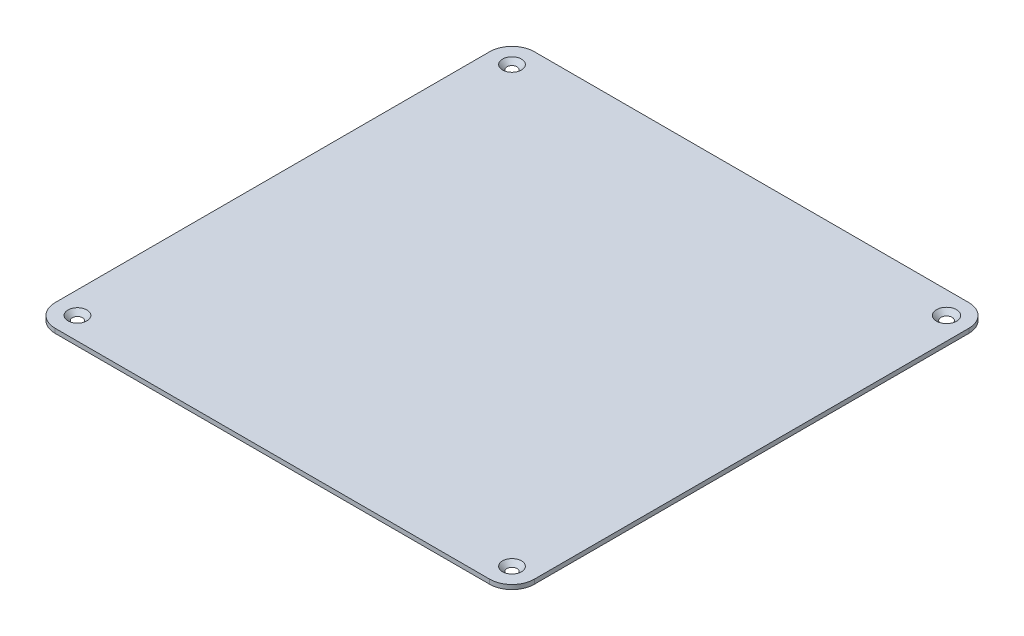
SolidWorks part; units mm, degrees
ref_plane "Front" through (0, 0, 0) normal (0, 0, 1) x (1, 0, 0)
ref_plane "Top" through (0, 0, 0) normal (0, 1, 0) x (1, 0, 0)
ref_plane "Right" through (0, 0, 0) normal (1, 0, 0) x (0, 0, -1)
sketch "Sketch1" plane through (0, 0, 0) normal (0, 1, 0) x (1, 0, 0)
  line L0 (0, 0) -> (0, 107.5) construction
  line L1 (0, 0) -> (107.5, 0) construction
  line L3 (-107.5, 107.5) -> (107.5, 107.5)
  line L4 (-107.5, 107.5) -> (-107.5, -107.5)
  line L5 (-107.5, -107.5) -> (107.5, -107.5)
  line L6 (107.5, 107.5) -> (107.5, -107.5)
  dimension "D1" = 215
extrude "Boss-Extrude1" add sketch "Sketch1" along normal blind 2
ref_plane "Plane1" through (60, 0, 0) normal (1, 0, 0) x (0, 0, -1)
ref_plane "Plane2" through (32.5, 0, 0) normal (1, 0, 0) x (0, 0, -1)
sketch "Sketch2" plane through (0, 2, 0) normal (0, 1, 0) x (1, 0, 0)
  line L0 (-97.5, -97.5) -> (-97.5, 97.5) construction
  line L1 (-97.5, 97.5) -> (97.5, 97.5) construction
  line L2 (97.5, 97.5) -> (97.5, -97.5) construction
  line L3 (97.5, -97.5) -> (-97.5, -97.5) construction
  line L4 (0, 0) -> (-107.5, 0) construction
  line L5 (-107.5, 107.5) -> (-107.5, -107.5) construction
  line L8 (0, 0) -> (0, -97.5) construction
  circle A0 centre (-97.5, 97.5) radius 2.25
  circle A1 centre (-97.5, -97.5) radius 2.25
  circle A2 centre (97.5, -97.5) radius 2.25
  circle A3 centre (97.5, 97.5) radius 2.5
  dimension "D1" = 4.5
  dimension "D2" = 195
extrude "Cut-Extrude1" cut sketch "Sketch2" against normal through all
chamfer "Chamfer1" distance 2 angle 45 4 edges at (97.5, 2, -95) (-97.5, 2, -95.25) (97.5, 2, 99.75) (-97.5, 2, 99.75)
fillet "Fillet1" radius 10 4 edges at (107.5, 1, -107.5) (-107.5, 1, -107.5) (107.5, 1, 107.5) (-107.5, 1, 107.5)
